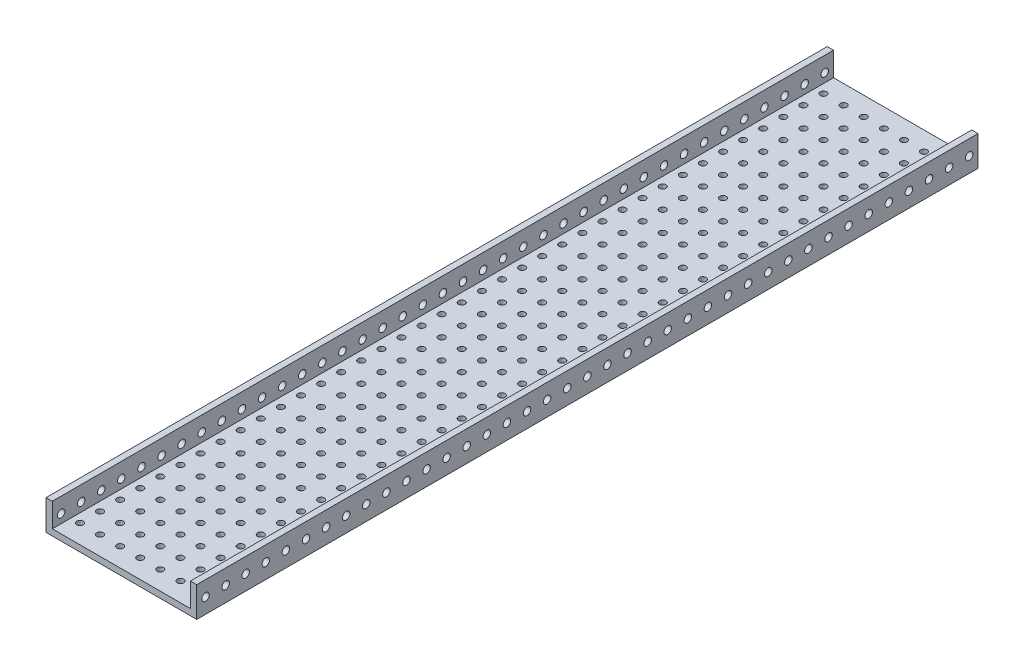
SolidWorks part; units mm, degrees
material "6061-T6 (SS)"
ref_plane "Front Plane" through (0, 0, 0) normal (0, 0, 1) x (1, 0, 0)
ref_plane "Top Plane" through (0, 0, 0) normal (0, 1, 0) x (1, 0, 0)
ref_plane "Right Plane" through (0, 0, 0) normal (1, 0, 0) x (0, 0, -1)
sketch "Sketch1" plane through (0, 0, 0) normal (0, 0, 1) x (1, 0, 0)
  line L0 (0, 0) -> (38.1, 0)
  line L1 (38.1, 0) -> (38.1, 15.24)
  line L2 (38.1, 15.24) -> (34.925, 15.24)
  line L3 (34.925, 15.24) -> (34.925, 3.175)
  line L4 (34.925, 3.175) -> (-34.925, 3.175)
  line L5 (-34.925, 3.175) -> (-34.925, 15.24)
  line L6 (-34.925, 15.24) -> (-38.1, 15.24)
  line L7 (-38.1, 15.24) -> (-38.1, 0)
  line L8 (-38.1, 0) -> (0, 0)
  dimension "D1" = 15.24
  dimension "D2" = 3.175
  dimension "D3" = 3.175
  dimension "D4" = 76.2
extrude "Extrude1" add sketch "Sketch1" along normal mid plane 394.97
sketch "Sketch2" plane through (0, 0, 0) normal (0, -1, 0) x (1, 0, 0)
  line L0 (-38.1, 197.485) -> (-30.48, 197.485) construction
  line L1 (-38.1, 197.485) -> (38.1, 197.485) construction
  line L2 (-30.48, 197.485) -> (-30.48, 191.135) construction
  dimension "D1" = 7.62
  dimension "D2" = 6.35
sketch "Sketch4" plane through (38.1, 0, 0) normal (1, 0, 0) x (0, 0, -1)
  line L0 (-197.485, 15.24) -> (-197.485, 7.62) construction
  line L1 (-197.485, 0) -> (-197.485, 15.24) construction
  line L2 (-197.485, 7.62) -> (-193.04, 7.62) construction
  line L3 (-193.04, 7.62) -> (-182.88, 7.62) construction
  dimension "D1" = 7.62
  dimension "D2" = 4.445
  dimension "D3" = 10.16
hole_wizard "#6 Clearance Hole1" positions "3DSketch1" profile "Sketch5" hole size "#6" standard "Ansi Inch" end condition through all
sketch3d "3DSketch1"
  point P0 (38.1, 7.62, 193.04)
sketch "Sketch5" plane through (38.1, 7.62, 193.04) normal (0, 1, 0) x (0, 0, -1)
  line L0 (0, 0) -> (0, 76.2)
  line L1 (0, 76.2) -> (1.8986, 76.2)
  line L2 (1.8986, 76.2) -> (1.8986, 0)
  line L5 (1.8986, 0) -> (0, 0)
  line L11 (0, -6.35) -> (0, 107.95) construction
  dimension "Thru Hole Dia." = 3.7973
  dimension "Thru Hole Depth" = 76.2
pattern_linear "LPattern1" count 39 spacing 10.16 along (0, 0, -1) of "#6 Clearance Hole1"
sketch "Sketch6" plane through (0, 0, 0) normal (0, -1, 0) x (1, 0, 0)
  line L0 (38.1, 187.96) -> (-38.1, 187.96) construction
  line L1 (0, 187.96) -> (5.08, 187.96) construction
  line L2 (0, 187.96) -> (-5.08, 187.96) construction
  line L5 (-38.1, 197.485) -> (38.1, 197.485) construction
  point P4 (0, 187.96)
  dimension "D1" = 5.08
  dimension "D2" = 5.08
  dimension "D3" = 9.525
hole_wizard "#4 Clearance Hole1" positions "3DSketch2" profile "Sketch7" hole size "#4" standard "Ansi Inch" end condition through all
sketch3d "3DSketch2"
  point P7 (0, 0, 187.96)
sketch "Sketch7" plane through (0, 0, 187.96) normal (1, 0, 0) x (0, 0, -1)
  line L0 (0, 0) -> (0, 15.24)
  line L1 (0, 15.24) -> (1.6319, 15.24)
  line L2 (1.6319, 15.24) -> (1.6319, 0)
  line L5 (1.6319, 0) -> (0, 0)
  line L11 (0, -6.35) -> (0, 107.95) construction
  dimension "Thru Hole Dia." = 3.2639
  dimension "Thru Hole Depth" = 15.24
pattern_linear "LPattern2" count 4 spacing 10.16 along (1, 0, 0) count 4 spacing 10.16 along (-1, 0, 0) of "#4 Clearance Hole1"
pattern_linear "LPattern3" count 38 spacing 10.16 along (0, 0, -1) of "LPattern2", "#4 Clearance Hole1"
